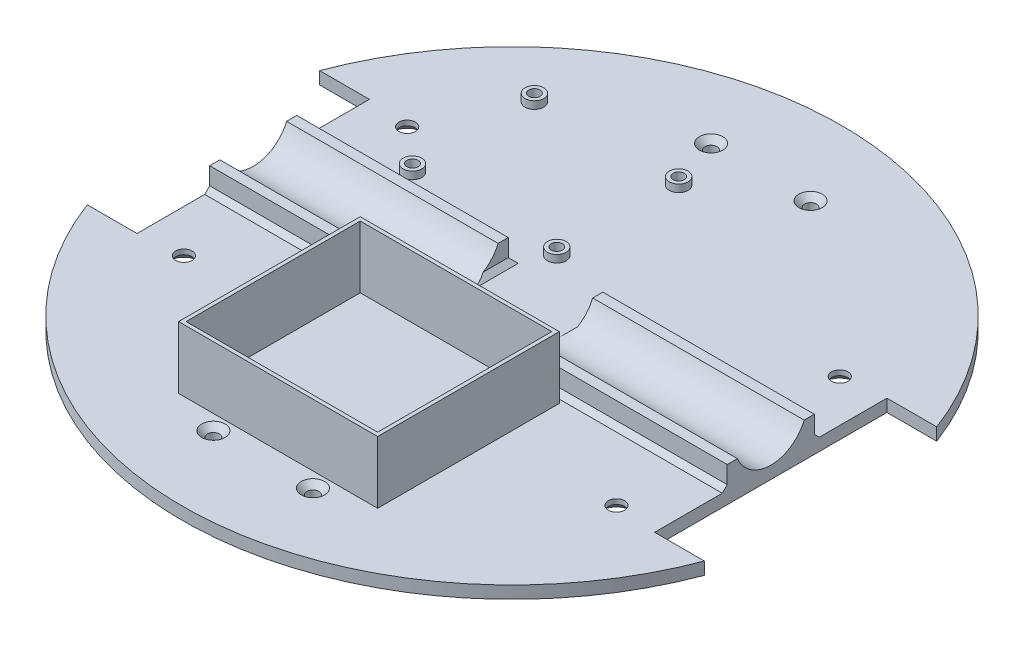
SolidWorks part; units mm, degrees
ref_plane "Alzado" through (0, 0, 0) normal (0, 0, 1) x (1, 0, 0)
ref_plane "Planta" through (0, 0, 0) normal (0, 1, 0) x (1, 0, 0)
ref_plane "Vista lateral" through (0, 0, 0) normal (1, 0, 0) x (0, 0, -1)
sketch "Croquis1" plane through (0, 0, 0) normal (0, 1, 0) x (1, 0, 0)
  circle A0 centre (0, 0) radius 132.5
  dimension "D1" = 265
extrude "Saliente-Extruir1" add sketch "Croquis1" along normal blind 5
sketch "Croquis5" plane through (0, 5, 0) normal (0, 1, 0) x (1, 0, 0)
  line L0 (132.5, 0) -> (-132.5, 0) construction
  line L1 (0, -132.5) -> (0, 132.5) construction
  circle A0 centre (0, 0) radius 132.5 construction
ref_plane "Plano1" through (0, 0, 0) normal (0, 0, -1) x (-1, 0, 0)
ref_plane "Plano2" through (0, 0, 0) normal (-1, 0, 0) x (0, 0, 1)
sketch "Croquis6" plane through (0, 5, 0) normal (0, 1, 0) x (1, 0, 0)
  line L0 (-104, 46.6931) -> (-104, -46.6931)
  line L1 (104, 46.6931) -> (104, -46.6931)
  line L4 (-124, 46.6931) -> (-104, 46.6931)
  line L5 (-124, -46.6931) -> (-104, -46.6931)
  line L6 (104, 46.6931) -> (124, 46.6931)
  line L7 (104, -46.6931) -> (124, -46.6931)
  arc A1 (124, -46.6931) -> (124, 46.6931) centre (0, 0) ccw
  arc A2 (124, -46.6931) -> (124, 46.6931) centre (0, 0) ccw
  arc A3 (-124, 46.6931) -> (-124, -46.6931) centre (0, 0) ccw
  arc A4 (-124, 46.6931) -> (-124, -46.6931) centre (0, 0) ccw
  dimension "D5" = 132.5
  dimension "D1" = 104
  dimension "D2" = 104
  dimension "D4" = 20
extrude "Cortar-Extruir4" cut sketch "Croquis6" against normal up to surface (5 mm away)
hole_wizard "Avellanado para tornillo con cabeza plana avellanada de M42" positions "Croquis24" profile "Croquis25" countersink size "M4" standard "ISO"
sketch "Croquis24" plane through (0, 0, 0) normal (0, -1, 0) x (-1, 0, 0)
  line L0 (123.75, 0) -> (-123.75, 0) construction
  line L5 (0, -132.5) -> (0, 132.5) construction
  point P0 (70, 30)
  point P2 (12, 30)
  point P4 (70, 79)
  point P6 (12, 79)
  dimension "D1" = 58
  dimension "D2" = 49
  dimension "D3" = 30
  dimension "D4" = 70
sketch "Croquis25" plane through (-70, 0, -30) normal (1, 0, 0) x (0, 0, -1)
  line L0 (0, 0) -> (0, 6.3509)
  line L1 (0, 6.3509) -> (2.25, 4.999)
  line L2 (2.25, 4.999) -> (2.25, 2.45)
  line L3 (2.25, 2.45) -> (4.7, 0)
  line L5 (4.7, 0) -> (0, 0)
  line L6 (-2.25, 2.45) -> (-4.7, 0) construction
  line L10 (0, 6.3509) -> (-2.25, 4.999) construction
  line L11 (0, -6.35) -> (0, 107.95) construction
  dimension "Diámetro de taladro" = 4.5
  dimension "Profundidad de taladro" = 4.999
  dimension "Ángulo de avellanado cercano" = 9.4
  dimension "Ángulo de avellanado lejano" = 90
  dimension "Ángulo de perforador" = 118
hole_wizard "Avellanado para tornillo con cabeza plana avellanada de M61" positions "Croquis3D1" profile "Croquis27" countersink size "M6" standard "ISO"
sketch3d "Croquis3D1"
  line L0 (0, 5, 132.5) -> (0, 5, -132.5) construction
  line L1 (132.5, 5, 0) -> (-132.5, 5, 0) construction
  point P0 (87, 0, 45)
  point P2 (-86.8562, 0, 45)
  point P26 (-86.8562, 0, -44.7214)
  point P28 (87, 0, -44.7214)
  dimension "D1" = 87
  dimension "D2" = 87
  dimension "D3" = 45
  dimension "D4" = 45
sketch "Croquis27" plane through (87, 0, 45) normal (1, 0, 0) x (0, 0, -1)
  line L0 (0, 0) -> (0, 6.9818)
  line L1 (0, 6.9818) -> (3.3, 4.999)
  line L2 (3.3, 4.999) -> (3.3, 3)
  line L3 (3.3, 3) -> (6.3, 0)
  line L5 (6.3, 0) -> (0, 0)
  line L6 (-3.3, 3) -> (-6.3, 0) construction
  line L10 (0, 6.9818) -> (-3.3, 4.999) construction
  line L11 (0, -6.35) -> (0, 107.95) construction
  dimension "Diámetro de taladro" = 6.6
  dimension "Profundidad de taladro" = 4.999
  dimension "Ángulo de avellanado cercano" = 12.6
  dimension "Ángulo de avellanado lejano" = 90
  dimension "Ángulo de perforador" = 118
hole_wizard "Avellanado para tornillo con cabeza plana avellanada de M43" positions "Croquis29" profile "Croquis30" countersink size "M4" standard "ISO"
sketch "Croquis29" plane through (0, 5, 0) normal (0, 1, 0) x (1, 0, 0)
  line L0 (123.75, 0) -> (-123.75, 0) construction
  line L1 (0, 123.75) -> (0, -123.75) construction
  point P0 (-20, -100)
  point P2 (20, -100)
  point P4 (-20, 100)
  point P6 (20, 100)
  dimension "D1" = 100
  dimension "D2" = 100
  dimension "D3" = 40
  dimension "D4" = 20
sketch "Croquis30" plane through (-20, 5, 100) normal (1, 0, 0) x (0, 0, 1)
  line L0 (0, 0) -> (0, 6.4411)
  line L1 (0, 6.4411) -> (2.4, 4.999)
  line L2 (2.4, 4.999) -> (2.4, 2.3)
  line L3 (2.4, 2.3) -> (4.7, 0)
  line L5 (4.7, 0) -> (0, 0)
  line L6 (-2.4, 2.3) -> (-4.7, 0) construction
  line L10 (0, 6.4411) -> (-2.4, 4.999) construction
  line L11 (0, -6.35) -> (0, 107.95) construction
  dimension "Diámetro de taladro" = 4.8
  dimension "Profundidad de taladro" = 4.999
  dimension "Ángulo de avellanado cercano" = 9.4
  dimension "Ángulo de avellanado lejano" = 90
  dimension "Ángulo de perforador" = 118
sketch "Croquis32" plane through (0, 5, 0) normal (0, 1, 0) x (1, 0, 0)
  line L0 (104, 46.6931) -> (104, -46.6931) construction
  line L1 (104, 17.5) -> (19, 17.5)
  line L2 (104, 17.5) -> (104, -17.5)
  line L3 (104, -17.5) -> (19, -17.5)
  line L4 (19, 17.5) -> (19, -17.5)
  line L5 (-104, 46.6931) -> (-104, -46.6931) construction
  line L6 (-104, 17.5) -> (-19, 17.5)
  line L7 (-104, 17.5) -> (-104, -17.5)
  line L8 (-104, -17.5) -> (-19, -17.5)
  line L9 (-19, 17.5) -> (-19, -17.5)
  dimension "D1" = 35
  dimension "D2" = 85
  dimension "D3" = 17.5
extrude "Saliente-Extruir6" add sketch "Croquis32" along normal blind 14.5
sketch "Croquis33" plane through (-104, 0, 0) normal (-1, 0, 0) x (0, 0, 1)
  line L0 (-17.5, 19.5) -> (17.5, 19.5) construction
  circle A0 centre (0, 19.5) radius 14.5
  dimension "D1" = 29
extrude "Cortar-Extruir8" cut sketch "Croquis33" against normal up to surface (208 mm away) up to face at (104, 7.375, 0)
sketch "Croquis34" plane through (-104, 0, 0) normal (-1, 0, 0) x (0, 0, 1)
  line L0 (-17.5, 19.5) -> (-17.5, 5) construction
  line L1 (-17.5, 19.5) -> (17.5, 19.5)
  line L2 (-17.5, 19.5) -> (-17.5, 14)
  line L3 (-17.5, 14) -> (17.5, 14)
  line L4 (17.5, 19.5) -> (17.5, 14)
  line L5 (17.5, 19.5) -> (17.5, 5) construction
  line L6 (-17.5, 19.5) -> (-17.5, 5) construction
  line L7 (17.5, 19.5) -> (17.5, 5) construction
  dimension "D1" = 5.5
extrude "Cortar-Extruir9" cut sketch "Croquis34" against normal up to surface (208 mm away) up to face at (104, 8.35, 0)
chamfer "Chaflán2" distance 2 angle 45 8 edges at (61.5, 5, -17.5) (-19, 5, 8.75) (-19, 5, -8.75) (-61.5, 5, -17.5) (-61.5, 5, 17.5) (19, 5, -8.75) (19, 5, 8.75) (61.5, 5, 17.5)
sketch "Croquis35" plane through (0, 5, 0) normal (0, 1, 0) x (1, 0, 0)
  line L1 (38.5, -92.5) -> (-38.5, -92.5)
  line L2 (38.5, -92.5) -> (38.5, -22.5)
  line L3 (38.5, -22.5) -> (-38.5, -22.5)
  line L4 (-38.5, -92.5) -> (-38.5, -22.5)
  line L5 (0, -92.5) -> (0, -22.5) construction
  line L6 (0, -132.5) -> (0, 132.5) construction
  line L7 (132.5, 0) -> (-132.5, 0) construction
  line L8 (40, -94) -> (-40, -94)
  line L9 (-40, -94) -> (-40, -21)
  line L10 (40, -21) -> (-40, -21)
  line L11 (40, -94) -> (40, -21)
  dimension "D1" = 70
  dimension "D2" = 77
  dimension "D3" = 22.5
  dimension "D4" = 1.5
extrude "Saliente-Extruir7" add sketch "Croquis35" along normal blind 25
sketch "Croquis36" plane through (0, 5, 0) normal (0, 1, 0) x (1, 0, 0)
  circle A0 centre (-70, 79) radius 3.75
  circle A1 centre (-12, 79) radius 3.75
  circle A2 centre (-12, 30) radius 3.75
  circle A3 centre (-70, 30) radius 3.75
  circle A4 centre (-70, 30) radius 2.25
  circle A5 centre (-70, 79) radius 2.25
  circle A6 centre (-12, 79) radius 2.25
  circle A7 centre (-12, 30) radius 2.25
  circle A8 centre (-70, 79) radius 2.25 construction
  dimension "D1" = 7.5
extrude "Saliente-Extruir8" add sketch "Croquis36" along normal blind 3
